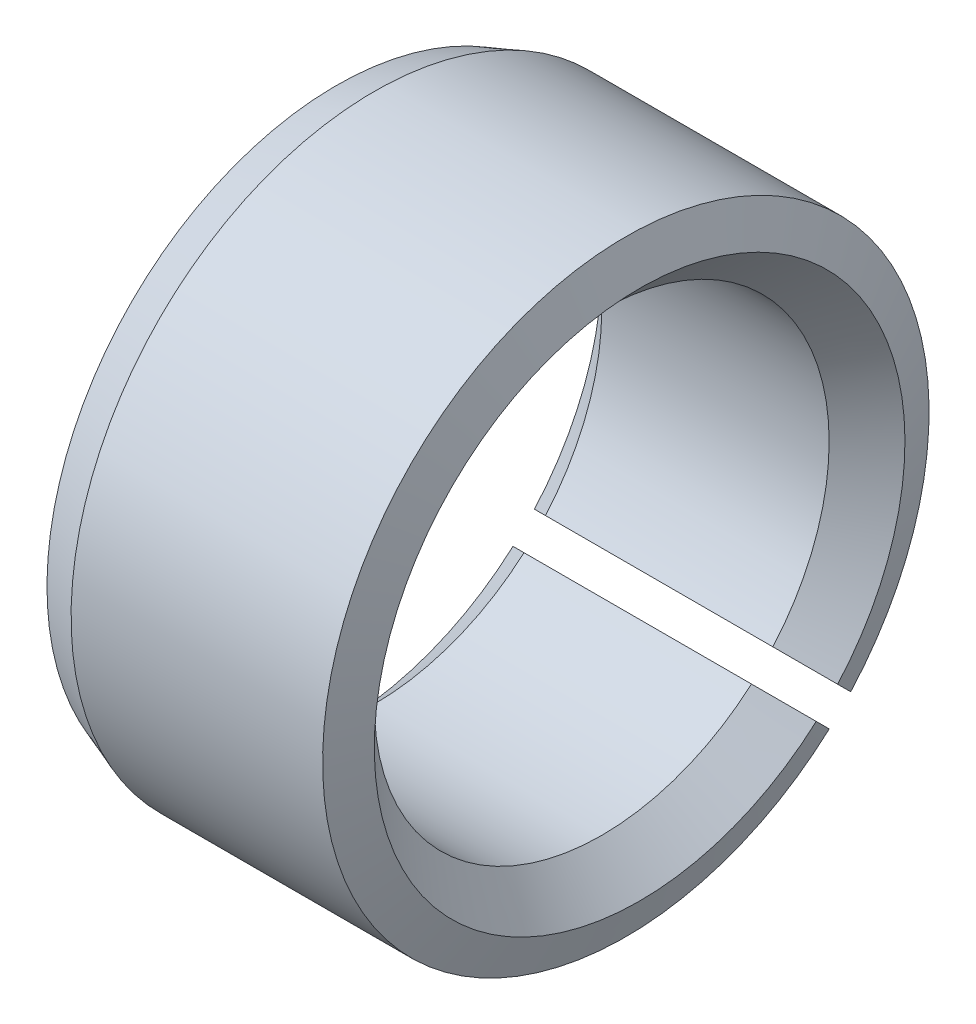
SolidWorks part; units mm, degrees
ref_plane "Plan de face" through (0, 0, 0) normal (0, 0, 1) x (1, 0, 0)
ref_plane "Plan de dessus" through (0, 0, 0) normal (0, 1, 0) x (1, 0, 0)
ref_plane "Plan de droite" through (0, 0, 0) normal (1, 0, 0) x (0, 0, -1)
sketch "Esquisse1" plane through (0, 0, 0) normal (0, 0, 1) x (1, 0, 0)
  line L0 (0, 4) -> (0, 0)
  line L1 (0, 0) -> (4, 0)
  line L2 (4, 0) -> (4, 4)
  line L3 (4, 4) -> (0, 4)
  line L4 (0, 0) -> (4, 0) construction
revolve "Révolution1" add sketch "Esquisse1" angle 360 about L4 reverse direction yes
sketch "Esquisse2" plane through (4, 0, 0) normal (1, 0, 0) x (0, 0, -1)
  line L0 (2.9663, -2.6835) -> (2.258, -1.9752)
  line L1 (1.9752, -2.258) -> (2.6835, -2.9663)
  arc A0 (2.258, -1.9752) -> (1.9752, -2.258) centre (0, 0) cw
  arc A1 (2.6835, -2.9663) -> (2.9663, -2.6835) centre (0, 0) ccw
extrude "Enlèv. mat.-Extru.1" cut sketch "Esquisse2" against normal through all
ref_plane "Plan1" through (0, 0, 0) normal (0, 0, -1) x (-1, 0, 0)
sketch "Esquisse3" plane through (0, 0, 0) normal (0, 0, -1) x (-1, 0, 0)
  line L0 (-4, 3) -> (-4, 0)
  line L1 (-4, 0) -> (0, 0)
  line L2 (0, 0) -> (0, 3)
  line L3 (0, 3) -> (-4, 3)
  line L4 (-4, 0) -> (0, 0) construction
revolve "Enlèvement de matière-Révolution1" cut sketch "Esquisse3" angle 360 about L4 reverse direction yes
chamfer "Chanfrein1" distance 0.5 angle 45 2 edges at (0, 2.1213, 2.1213) (4, 2.1213, 2.1213)
chamfer "Chanfrein2" distance 0.182 angle 70 2 edges at (4, 2.8284, 2.8284) (0, 2.8284, 2.8284) first distance on face at (2, 0.0018, 0.0018) first distance on face at (0, 0.0019, 0.0019)
